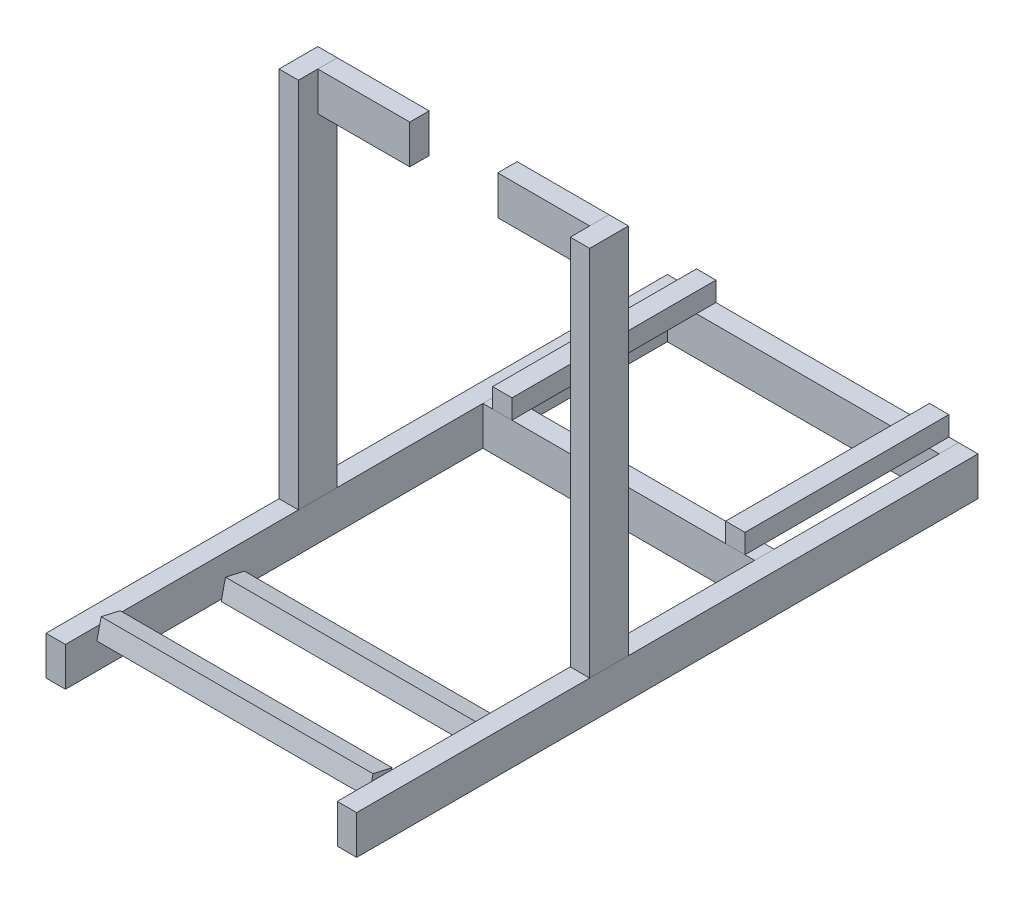
SolidWorks part; units mm, degrees
material "6061-T6 (SS)"
ref_plane "Front Plane" through (0, 0, 0) normal (0, 0, 1) x (1, 0, 0)
ref_plane "Top Plane" through (0, 0, 0) normal (0, 1, 0) x (1, 0, 0)
ref_plane "Right Plane" through (0, 0, 0) normal (1, 0, 0) x (0, 0, -1)
sketch "Sketch1" plane through (0, 0, 0) normal (0, 0, 1) x (1, 0, 0)
  line L0 (0, -90.2611) -> (0, 372.4246) construction
  line L1 (-266.7, 19.05) -> (-266.7, 95.25)
  line L2 (266.7, 19.05) -> (304.8, 19.05)
  line L3 (266.7, 19.05) -> (266.7, 95.25)
  line L4 (266.7, 95.25) -> (304.8, 95.25)
  line L5 (304.8, 19.05) -> (304.8, 95.25)
  line L6 (-266.7, 19.05) -> (-304.8, 19.05)
  line L7 (-304.8, 19.05) -> (-304.8, 95.25)
  line L8 (-266.7, 95.25) -> (-304.8, 95.25)
  dimension "D2" = 76.2
  dimension "D1" = 533.4
  dimension "D4" = 19.05
extrude "Boss-Extrude1" add sketch "Sketch1" against normal blind 1219.2
sketch "Sketch2" plane through (0, 0, 0) normal (1, 0, 0) x (0, 0, -1)
  line L0 (1219.2, 19.05) -> (0, 19.05) construction
  line L1 (1219.2, 95.25) -> (1181.1, 95.25)
  line L2 (1219.2, 95.25) -> (1219.2, 19.05)
  line L3 (1219.2, 19.05) -> (1181.1, 19.05)
  line L4 (1181.1, 95.25) -> (1181.1, 19.05)
  line L5 (857.25, 95.25) -> (819.15, 95.25)
  line L6 (857.25, 95.25) -> (857.25, 19.05)
  line L7 (857.25, 19.05) -> (819.15, 19.05)
  line L8 (819.15, 95.25) -> (819.15, 19.05)
  dimension "D1" = 38.1
  dimension "D2" = 76.2
  dimension "D4" = 38.1
  dimension "D5" = 400.05
extrude "Boss-Extrude2" add sketch "Sketch2" along normal up to next (266.7 mm away) and the other way up to next (266.7 mm away) separate body
sketch "Sketch3" plane through (0, 95.25, 0) normal (0, 1, 0) x (1, 0, 0)
  line L0 (0, -1000) -> (0, 49000) construction
  line L1 (-266.7, 457.2) -> (-266.7, 533.4)
  line L2 (266.7, 457.2) -> (304.8, 457.2)
  line L3 (266.7, 457.2) -> (266.7, 533.4)
  line L4 (266.7, 533.4) -> (304.8, 533.4)
  line L5 (304.8, 457.2) -> (304.8, 533.4)
  line L6 (-266.7, 457.2) -> (-304.8, 457.2)
  line L7 (-304.8, 457.2) -> (-304.8, 533.4)
  line L8 (-266.7, 533.4) -> (-304.8, 533.4)
  line L9 (266.7, 1219.2) -> (266.7, 0) construction
  line L10 (304.8, 0) -> (266.7, 0) construction
  dimension "D1" = 38.1
  dimension "D2" = 76.2
  dimension "D3" = 457.2
extrude "Boss-Extrude3" add sketch "Sketch3" along normal blind 730.25 separate body
sketch "Sketch4" plane through (0, 0, -819.15) normal (0, 0, 1) x (1, 0, 0)
  line L0 (0, -1002.4675) -> (0, 48997.5325) construction
  line L1 (-209.55, 133.35) -> (-209.55, 95.25)
  line L2 (209.55, 133.35) -> (247.65, 133.35)
  line L3 (209.55, 133.35) -> (209.55, 95.25)
  line L4 (209.55, 95.25) -> (247.65, 95.25)
  line L5 (247.65, 133.35) -> (247.65, 95.25)
  line L6 (-209.55, 133.35) -> (-247.65, 133.35)
  line L7 (-247.65, 133.35) -> (-247.65, 95.25)
  line L8 (-209.55, 95.25) -> (-247.65, 95.25)
  line L9 (-266.7, 95.25) -> (266.7, 95.25) construction
  point P13 (228.6, 133.35)
  point P14 (-228.6, 133.35)
  dimension "D1" = 38.1
  dimension "D3" = 457.2
  dimension "D2" = 38.1
extrude "Boss-Extrude4" add sketch "Sketch4" against normal blind 400.05 separate body
sketch "Sketch6" plane through (0, 0, 0) normal (1, 0, 0) x (0, 0, -1)
  line L0 (61.7895, 70.1417) -> (70.1417, 107.3149)
  line L25 (70.1417, 107.3149) -> (107.3149, 98.9627)
  line L26 (107.3149, 98.9627) -> (98.9627, 61.7895)
  line L27 (-609.6, 76.2) -> (-560.5375, 76.2) construction
  line L28 (98.9627, 61.7895) -> (61.7895, 70.1417)
  line L29 (-609.6, 38.1) -> (-553.7974, 38.1) construction
  line L30 (1219.2, 95.25) -> (0, 95.25) construction
  line L31 (1219.2, 19.05) -> (0, 19.05) construction
  line L32 (305.7085, 15.3373) -> (314.0607, 52.5105)
  line L33 (314.0607, 52.5105) -> (351.2339, 44.1583)
  line L34 (351.2339, 44.1583) -> (342.8817, 6.9851)
  line L35 (342.8817, 6.9851) -> (305.7085, 15.3373)
  line L36 (70.1417, 107.3149) -> (98.9627, 61.7895) construction
  line L37 (314.0607, 52.5105) -> (342.8817, 6.9851) construction
  line L38 (76.2, 47.3789) -> (92.9044, 121.7254) construction
  line L39 (47.3789, 92.9044) -> (121.7254, 76.2) construction
  line L40 (320.119, -7.4254) -> (336.8234, 66.9211) construction
  line L41 (291.2979, 38.1) -> (365.6444, 21.3956) construction
  line L42 (0, 19.05) -> (0, 95.25) construction
  point P13 (88.7283, 103.1388)
  point P14 (332.6473, 48.3344)
  point P21 (84.5522, 84.5522)
  point P22 (84.5522, 84.5522)
  point P23 (84.5522, 84.5522)
  point P24 (328.4712, 29.7478)
  point P25 (328.4712, 29.7478)
  point P26 (328.4712, 29.7478)
  dimension "D1" = 38.1
  dimension "D4" = 38.1
  dimension "D2" = 38.1
  dimension "D8" = 19.05
  dimension "D6" = 19.05
  dimension "D5" = 250
  dimension "D7" = 76.2
  dimension "D9" = 76.2
  dimension "D10" = 12.663
  dimension "D11" = 76.2
extrude "Boss-Extrude5" add sketch "Sketch6" along normal up to surface (266.7 mm away) and the other way up to surface (266.7 mm away) separate body up to face at (266.7, 57.15, -609.6) other way up to face at (-266.7, 57.15, -609.6)
sketch "Sketch7" plane through (0, 0, 0) normal (1, 0, 0) x (0, 0, -1)
  line L0 (533.4, 825.5) -> (533.4, 95.25) construction
  line L1 (533.4, 825.5) -> (495.3, 825.5)
  line L2 (533.4, 825.5) -> (533.4, 749.3)
  line L3 (533.4, 749.3) -> (495.3, 749.3)
  line L4 (495.3, 825.5) -> (495.3, 749.3)
  line L5 (1219.2, 95.25) -> (0, 95.25) construction
  dimension "D1" = 38.1
  dimension "D2" = 76.2
  dimension "D3" = 654.05
extrude "Boss-Extrude6" add sketch "Sketch7" along normal up to next (266.7 mm away) and the other way up to next (266.7 mm away) separate body
extrude "Cut-Extrude1" cut sketch "Sketch7<2>" against normal mid plane 172.7
sketch "Sketch7<2>" plane through (0, 0, 0) normal (1, 0, 0) x (0, 0, -1) same geometry as "Sketch7"
sketch "Sketch8" plane through (0, 0, 0) normal (1, 0, 0) x (0, 0, -1)
  line L1 (495.3, 1047.75) -> (533.4, 1047.75)
  line L2 (495.3, 1047.75) -> (495.3, 1009.65)
  line L3 (495.3, 1009.65) -> (533.4, 1009.65)
  line L4 (533.4, 1047.75) -> (533.4, 1009.65)
  line L5 (1219.2, 95.25) -> (0, 95.25) construction
  line L6 (533.4, 825.5) -> (533.4, 95.25) construction
  dimension "D1" = 38.1
  dimension "D2" = 38.1
  dimension "D3" = 914.4
extrude "Boss-Extrude7" [suppressed] add sketch "Sketch8" along normal mid plane 965.2 separate body
equation "\"W 1.5\"= 1.5"
equation "\"D1@Sketch2\"=\"W 1.5\""
equation "\"H 3\"= 3"
equation "\"D2@Sketch2\"=\"H 3\""
equation "\"D4@Sketch2\"=\"W 1.5\""
equation "\"D3@Sketch2\"=\"H 3\""
equation "\"D3@Sketch1\"=\"W 1.5\""
equation "\"D2@Sketch1\"=\"H 3\""
equation "\"D1@Sketch3\"=\"W 1.5\""
equation "\"D2@Sketch3\"=\"H 3\""
equation "\"H 1.5\"= 1.5"
equation "\"D1@Sketch4\"=\"W 1.5\""
equation "\"D2@Sketch4\"=\"H 1.5\""
equation "\"D1@Sketch6\"=\"W 1.5\""
equation "\"D2@Sketch6\"=\"W 1.5\""
equation "\"D3@Sketch6\"=\"H 1.5\""
equation "\"D4@Sketch6\"=\"H 1.5\""
equation "\"D1@Sketch7\"=\"W 1.5\""
equation "\"D2@Sketch7\"=\"H 3\""
equation "\"D1@Sketch8\"=\"W 1.5\""
equation "\"D2@Sketch8\"=\"H 1.5\""
